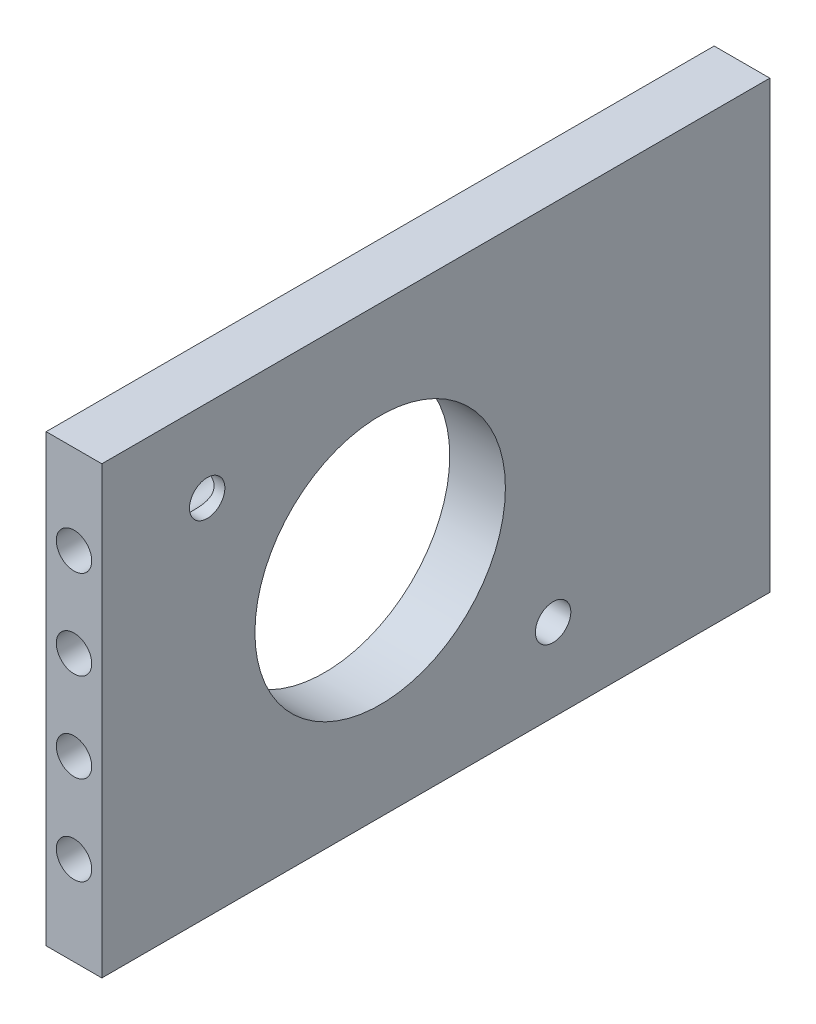
SolidWorks part; units mm, degrees
material "6061-T6 (SS)"
ref_plane "Front" through (0, 0, 0) normal (0, 0, 1) x (1, 0, 0)
ref_plane "Top" through (0, 0, 0) normal (0, 1, 0) x (1, 0, 0)
ref_plane "Right" through (0, 0, 0) normal (1, 0, 0) x (0, 0, -1)
sketch "Sketch2" plane through (0, 0, 0) normal (1, 0, 0) x (0, 0, -1)
  line L1 (-38.1, -25.4) -> (38.1, -25.4)
  line L2 (-38.1, -25.4) -> (-38.1, 25.4)
  line L3 (-38.1, 25.4) -> (38.1, 25.4)
  line L4 (38.1, -25.4) -> (38.1, 25.4)
  line L5 (-38.1, -25.4) -> (38.1, 25.4) construction
  line L6 (-38.1, 25.4) -> (38.1, -25.4) construction
  point P0 (0, 0)
  dimension "D1" = 76.2
  dimension "D2" = 50.8
extrude "Boss-Extrude2" add sketch "Sketch2" along normal blind 6.35
hole_wizard "#10-32 Tapped Hole1" positions "Sketch3" profile "Sketch5" tap size "#10-32" standard "ANSI Inch"
sketch "Sketch3" plane through (0, 0, 38.1) normal (0, 0, 1) x (1, 0, 0)
  line L0 (3.175, 25.4) -> (3.175, 15.24) construction
  line L1 (6.35, 25.4) -> (0, 25.4) construction
  line L2 (3.175, 15.24) -> (3.175, 5.08) construction
  line L3 (3.175, 5.08) -> (3.175, -5.08) construction
  line L4 (3.175, -5.08) -> (3.175, -15.24) construction
  line L5 (3.175, -15.24) -> (3.175, -25.4) construction
  line L6 (6.35, -25.4) -> (0, -25.4) construction
  point P0 (3.175, -15.24)
  point P2 (3.175, -5.08)
  point P4 (3.175, 5.08)
  point P6 (3.175, 15.24)
sketch "Sketch5" plane through (3.175, -15.24, 38.1) normal (1, 0, 0) x (0, -1, 0)
  line L0 (0, 0) -> (0, 26.6133)
  line L1 (0, 26.6133) -> (2.0193, 25.4)
  line L2 (2.0193, 25.4) -> (2.0193, 0)
  line L5 (2.0193, 0) -> (0, 0)
  line L10 (0, 26.6133) -> (-2.0193, 25.4) construction
  line L11 (0, -6.35) -> (0, 107.95) construction
  dimension "Tap Drill Dia." = 4.0386
  dimension "Tap Drill Depth" = 25.4
  dimension "Drill Angle" = 118
cosmetic thread "Hole Thread1" parameters "D1"=9.652, "D2"=4.826
cosmetic thread "Hole Thread2" parameters "D1"=9.652, "D2"=4.826
cosmetic thread "Hole Thread3" parameters "D1"=9.652, "D2"=4.826
cosmetic thread "Hole Thread4" parameters "D1"=9.652, "D2"=4.826
sketch "Sketch6" plane through (6.35, 0, 0) normal (1, 0, 0) x (0, 0, -1)
  line L0 (-38.1, 25.4) -> (-38.1, -25.4) construction
  line L1 (-38.1, -25.4) -> (38.1, -25.4) construction
  circle A0 centre (-6.35, 0) radius 14.2875
  dimension "D1" = 31.75
  dimension "D3" = 28.575
  dimension "D2" = 25.4
extrude "Cut-Extrude1" cut sketch "Sketch6" against normal through all
sketch "Sketch10" plane through (0, 0, 0) normal (-1, 0, 0) x (0, 0, 1)
  point P0 (26.0863, 16.0082)
  point P3 (-13.3773, -15.9803)
hole_wizard "#10-32 Tapped Hole2" positions "Sketch10" profile "Sketch9" tap size "#10-32" standard "ANSI Inch"
sketch "Sketch9" plane through (0, 16.0082, 26.0863) normal (0, 1, 0) x (0, 0, 1)
  line L0 (0, 0) -> (0, 13.2428)
  line L1 (0, 13.2428) -> (2.0193, 12.0294)
  line L2 (2.0193, 12.0294) -> (2.0193, 0)
  line L5 (2.0193, 0) -> (0, 0)
  line L10 (0, 13.2428) -> (-2.0193, 12.0294) construction
  line L11 (0, -6.35) -> (0, 107.95) construction
  dimension "Tap Drill Dia." = 4.0386
  dimension "Tap Drill Depth" = 12.0294
  dimension "Drill Angle" = 118
cosmetic thread "Hole Thread5" parameters "D1"=9.652, "D2"=4.826
cosmetic thread "Hole Thread6" parameters "D1"=9.652, "D2"=4.826
